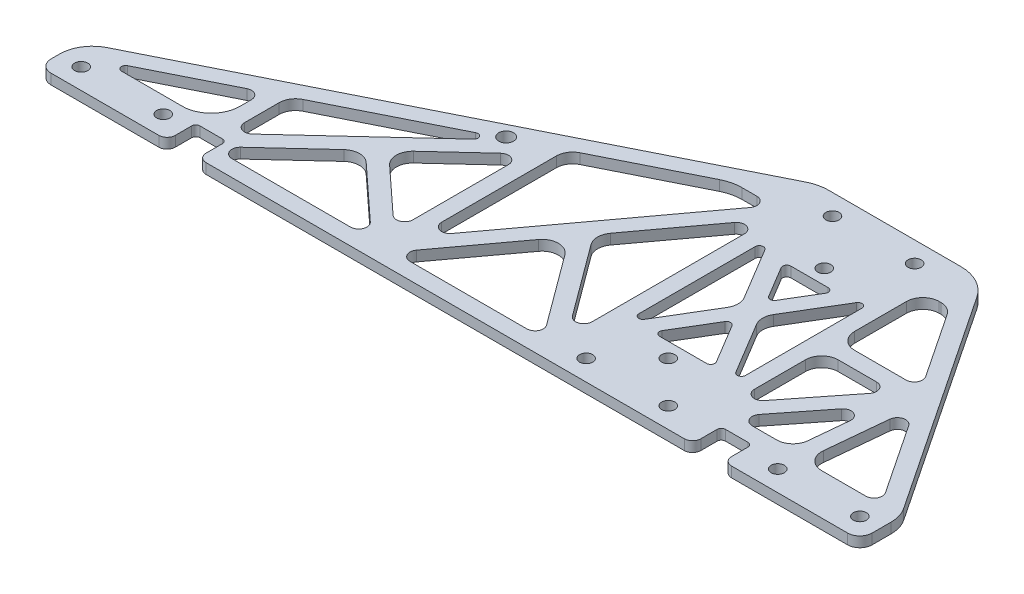
SolidWorks part; units mm, degrees
ref_plane "Front Plane" through (0, 0, 0) normal (0, 0, 1) x (1, 0, 0)
ref_plane "Top Plane" through (0, 0, 0) normal (0, 1, 0) x (1, 0, 0)
ref_plane "Right Plane" through (0, 0, 0) normal (1, 0, 0) x (0, 0, -1)
sketch "Sketch1" plane through (0, 0, 0) normal (0, 1, 0) x (1, 0, 0)
  line L0 (0, 0) -> (254, 0)
  line L2 (203.2, 88.9) -> (152.4, 88.9)
  line L4 (0, 0) -> (0, 12.7)
  line L5 (0, 12.7) -> (152.4, 88.9)
  line L6 (203.2, 88.9) -> (254, 12.7)
  line L7 (254, 12.7) -> (254, 0)
  line L8 (0, 6.35) -> (44.45, 6.35) construction
  line L9 (254, 6.35) -> (222.25, 6.35) construction
  line L10 (139.7, 82.55) -> (207.4333, 82.55) construction
  line L11 (44.45, 0) -> (44.45, 34.925) construction
  line L12 (156.6333, 12.7) -> (154.0933, 7.62)
  line L13 (224.7006, 47.4909) -> (221.314, 12.7) construction
  line L20 (127, 76.2) -> (211.6667, 76.2)
  line L21 (154.0933, 76.2) -> (101.6, 5.08) construction
  line L22 (154.0933, 12.7) -> (154.0933, 7.62)
  line L23 (247.8946, 12.7) -> (194.7333, 12.7)
  line L24 (224.7006, 47.4909) -> (197.2733, 12.7) construction
  line L28 (224.7006, 47.4909) -> (194.7333, 47.4909) construction
  line L31 (5.08, 9.5604) -> (153.5992, 83.82)
  line L32 (200.4813, 83.82) -> (153.5992, 83.82)
  line L33 (200.4813, 83.82) -> (248.92, 11.1619)
  line L34 (248.92, 11.1619) -> (248.92, 5.08)
  line L35 (5.08, 5.08) -> (248.92, 5.08)
  line L36 (5.08, 5.08) -> (5.08, 9.5604)
  line L37 (101.6, 5.08) -> (101.6, 57.8204) construction
  line L39 (127.8467, 40.64) -> (154.0933, 5.08) construction
  line L40 (101.6, 57.8204) -> (44.45, 5.08) construction
  line L41 (73.025, 31.4502) -> (101.6, 5.08) construction
  line L42 (154.0933, 7.62) -> (154.0933, 5.08)
  line L83 (152.8233, 5.08) -> (150.2833, 0)
  line L84 (125.803, 39.1316) -> (152.0497, 3.5716)
  line L107 (152.0497, 77.7084) -> (99.5564, 6.5884)
  line L108 (156.6333, 76.2) -> (194.7333, 12.7) construction
  line L113 (194.7333, 76.2) -> (156.6333, 12.7) construction
  line L117 (104.14, 5.08) -> (104.14, 63.6207)
  line L118 (156.6333, 12.7) -> (194.7333, 12.7)
  line L119 (194.7333, 12.7) -> (201.0833, 0)
  line L120 (154.0933, 6.35) -> (197.9083, 6.35) construction
  line L126 (192.5553, 77.5068) -> (154.4553, 14.0068)
  line L127 (154.4553, 74.8932) -> (192.5553, 11.3932)
  line L128 (156.6333, 12.7) -> (156.6333, 76.2) construction
  line L129 (194.7333, 12.7) -> (194.7333, 76.2) construction
  line L130 (197.2733, 12.7) -> (197.2733, 76.2)
  line L131 (159.1733, 12.7) -> (159.1733, 76.2)
  line L132 (192.1933, 12.7) -> (192.1933, 76.2)
  line L133 (154.0933, 12.7) -> (154.0933, 76.2)
  line L147 (196.9114, 74.8932) -> (158.8114, 11.3932)
  line L148 (158.8114, 77.5068) -> (196.9114, 14.0068)
  line L154 (104.14, 63.6207) -> (42.7274, 6.9466)
  line L155 (71.3024, 29.5836) -> (99.8774, 3.2134)
  line L156 (224.7006, 50.0309) -> (194.7333, 50.0309)
  line L157 (222.7059, 49.0635) -> (195.2786, 14.2725)
  line L158 (197.2733, 12.7) -> (197.2733, 7.62)
  line L159 (222.1726, 47.737) -> (218.7859, 12.9461)
  line L160 (129.8903, 42.1484) -> (156.137, 6.5884)
  line L163 (156.137, 74.6916) -> (103.6436, 3.5716)
  line L164 (99.06, 5.08) -> (99.06, 52.0201)
  line L165 (99.06, 52.0201) -> (46.1726, 3.2134)
  line L166 (175.6833, 19.05) -> (162.9833, 6.35) construction
  line L167 (175.6833, 19.05) -> (188.3833, 6.35) construction
  line L168 (162.9833, 82.55) -> (175.6833, 67.31) construction
  line L169 (175.6833, 67.31) -> (188.3833, 82.55) construction
  line L170 (161.6625, 21.082) -> (189.7041, 21.082) construction
  line L171 (161.6625, 23.622) -> (189.7041, 23.622)
  line L172 (163.1865, 65.278) -> (188.1801, 65.278) construction
  line L173 (163.1865, 62.738) -> (188.1801, 62.738)
  line L174 (74.7476, 33.3168) -> (103.3226, 6.9466)
  line L175 (224.7006, 44.9509) -> (194.7333, 44.9509)
  line L176 (226.6953, 45.9184) -> (199.268, 11.1275)
  line L177 (227.2287, 47.2449) -> (223.842, 12.4539)
  line L178 (8.8192, 11.43) -> (44.45, 11.43)
  line L179 (46.99, 0) -> (46.99, 34.925)
  line L180 (41.91, 0) -> (41.91, 34.925)
  line L181 (198.2745, 13.97) -> (221.4376, 13.97)
  circle A0 centre (6.7733, 6.35) radius 2.032
  circle A1 centre (32.1733, 6.35) radius 2.032
  circle A2 centre (222.25, 6.35) radius 2.032
  circle A3 centre (247.65, 6.35) radius 2.032
  circle A4 centre (162.9833, 82.55) radius 2.032
  circle A5 centre (188.3833, 82.55) radius 2.032
  circle A28 centre (162.9833, 6.35) radius 2.032
  circle A29 centre (188.3833, 6.35) radius 2.032
  arc A32 (197.2733, 12.7) -> (192.1933, 12.7) centre (194.7333, 12.7) cw
  arc A33 (197.2733, 76.2) -> (192.1933, 76.2) centre (194.7333, 76.2) ccw
  arc A34 (159.1733, 12.7) -> (154.0933, 12.7) centre (156.6333, 12.7) cw
  arc A35 (159.1733, 76.2) -> (154.0933, 76.2) centre (156.6333, 76.2) ccw
  arc A45 (192.5553, 77.5068) -> (196.9114, 74.8932) centre (194.7333, 76.2) cw
  arc A46 (154.4553, 14.0068) -> (158.8114, 11.3932) centre (156.6333, 12.7) ccw
  arc A47 (154.4553, 74.8932) -> (158.8114, 77.5068) centre (156.6333, 76.2) cw
  arc A48 (192.5553, 11.3932) -> (196.9114, 14.0068) centre (194.7333, 12.7) ccw
  circle A59 centre (175.6833, 19.05) radius 2.032
  circle A60 centre (175.6833, 67.31) radius 2.032
  arc A61 (125.803, 39.1316) -> (129.8903, 42.1484) centre (127.8467, 40.64) cw
  arc A62 (152.0497, 3.5716) -> (156.137, 6.5884) centre (154.0933, 5.08) ccw
  arc A63 (152.0497, 77.7084) -> (156.137, 74.6916) centre (154.0933, 76.2) cw
  arc A64 (99.5564, 6.5884) -> (103.6436, 3.5716) centre (101.6, 5.08) ccw
  arc A65 (104.14, 5.08) -> (99.06, 5.08) centre (101.6, 5.08) cw
  arc A66 (42.7274, 6.9466) -> (46.1726, 3.2134) centre (44.45, 5.08) ccw
  arc A67 (71.3024, 29.5836) -> (74.7476, 33.3168) centre (73.025, 31.4502) cw
  arc A68 (99.8774, 3.2134) -> (103.3226, 6.9466) centre (101.6, 5.08) ccw
  arc A69 (224.7006, 50.0309) -> (224.7006, 44.9509) centre (224.7006, 47.4909) cw
  arc A70 (194.7333, 50.0309) -> (194.7333, 44.9509) centre (194.7333, 47.4909) ccw
  arc A71 (222.7059, 49.0635) -> (226.6953, 45.9184) centre (224.7006, 47.4909) cw
  arc A72 (195.2786, 14.2725) -> (199.268, 11.1275) centre (197.2733, 12.7) ccw
  arc A73 (222.1726, 47.737) -> (227.2287, 47.2449) centre (224.7006, 47.4909) cw
  arc A74 (218.7859, 12.9461) -> (223.842, 12.4539) centre (221.314, 12.7) ccw
  arc A75 (46.99, 0) -> (41.91, 0) centre (44.45, 0) cw
  arc A76 (46.99, 34.925) -> (41.91, 34.925) centre (44.45, 34.925) ccw
  dimension "D7" = 4.064
  dimension "D8" = 25.4
  dimension "D9" = 130.81
  dimension "D10" = 25.4
  dimension "D11" = 6.35
  dimension "D13" = 19.05
  dimension "D1" = 254
  dimension "D2" = 50.8
  dimension "D3" = 88.9
  dimension "D4" = 152.4
  dimension "D5" = 12.7
  dimension "D6" = 6.35
  dimension "D12" = 25.4
  dimension "D14" = 44.45
  dimension "D15" = 12.7
  dimension "D16" = 57.15
  dimension "D18" = 12.7
  dimension "D19" = 2.54
  dimension "D20" = 50.8
  dimension "D21" = 25.4
  dimension "D22" = 2.54
  dimension "D23" = 6.35
  dimension "D24" = 2.54
  dimension "D29" = 6.35
  dimension "D30" = 38.1
  dimension "D31" = 25.4
  dimension "D32" = 6.35
  dimension "D33" = 2.54
  dimension "D36" = 12.7
  dimension "D38" = 15.24
  dimension "D39" = 2.54
  dimension "D40" = 2.54
  dimension "D27" = 1.27
  dimension "D17" = 5.08
  dimension "D25" = 2.54
  dimension "D26" = 2.54
  dimension "D37" = 2.54
extrude "Boss-Extrude1" add sketch "Sketch1" along normal blind 3.175 contours L0 L7 L6 L2 L5 L4 | A0 | A1 | A5 | A4 | A2 | A3
extrude "Cut-Extrude2" cut sketch "Sketch1<3>" along normal through all contours L154 L31 L11 | L155 L165 L35 | L165 L174 L164 | L117 L107 L20 L31 | L84 L163 L35 | L133 L163 L160 L22 | L157 L175 L130 | L156 L33 L20 L130 | L147 L148 L132 | L131 L126 L127 | L173 L148 L126 | L147 L171 L127 | L33 L177 L23 | L178 L180 L31 | L176 L181 L159 | A28 | A59 | A29 | A60 region at (30.8797, 0, -16.9451) region at (73.025, 0, -12.718) region at (62.4687, 0, -31.7097) region at (120.7695, 0, -51.2726) region at (127.8467, 0, -15.5076) region at (91.6301, 0, -31.4502) region at (206.5243, 0, -60.8789) region at (146.3968, 0, -40.64) region at (204.6702, 0, -35.5682) region at (175.6833, 0, -28.919) region at (187.6774, 0, -44.45) region at (213.9093, 0, -22.3524) region at (163.6893, 0, -44.45) region at (232.896, 0, -23.1836) region at (175.6833, 0, -58.2876)
sketch "Sketch1<3>" plane through (0, 0, 0) normal (0, 1, 0) x (1, 0, 0) same geometry as "Sketch1"
fillet "Fillet1" radius 3.81 2 edges at (254, 1.5875, 0) (0, 1.5875, 0)
fillet "Fillet2" radius 10.16 2 edges at (254, 1.5875, -12.7) (0, 1.5875, -12.7)
fillet "Fillet3" radius 12.7 2 edges at (203.2, 1.5875, -88.9) (152.4, 1.5875, -88.9)
fillet "Fillet4" radius 1.27 12 edges at (159.1733, 1.5875, -67.0298) (192.1933, 1.5875, -67.0298) (192.1933, 1.5875, -21.8702) (159.1733, 1.5875, -21.8702) (183.694, 1.5875, -62.738) (167.6727, 1.5875, -62.738) (175.6833, 1.5875, -49.3869) (185.218, 1.5875, -23.622) (166.1487, 1.5875, -23.622) (175.6833, 1.5875, -39.5131) (93.426, 1.5875, -53.7334) (8.8192, 1.5875, -11.43)
fillet "Fillet5" radius 2.54 19 edges at (223.0073, 1.5875, -50.0309) (247.8946, 1.5875, -12.7) (226.9275, 1.5875, -44.1507) (221.3335, 1.5875, -39.1171) (197.2733, 1.5875, -16.8027) (219.4639, 1.5875, -44.9509) (104.14, 1.5875, -12.7984) (99.06, 1.5875, -52.0201) (48.1953, 1.5875, -5.08) (97.8547, 1.5875, -5.08) (99.06, 1.5875, -10.8803) (104.7569, 1.5875, -5.08) (150.9364, 1.5875, -5.08) (154.0933, 1.5875, -9.3572) (154.0933, 1.5875, -71.9228) (150.9364, 1.5875, -76.2) (41.91, 1.5875, -27.9754) (46.99, 1.5875, -10.8803) (201.5089, 1.5875, -13.97)
fillet "Fillet6" radius 5.08 14 edges at (172.7212, 1.5875, -44.45) (178.6455, 1.5875, -44.45) (223.866, 1.5875, -12.7) (197.2733, 1.5875, -50.0309) (197.2733, 1.5875, -44.9509) (197.2733, 1.5875, -76.2) (205.5613, 1.5875, -76.2) (73.025, 1.5875, -27.9939) (76.7703, 1.5875, -31.4502) (104.14, 1.5875, -59.0904) (131.0036, 1.5875, -40.64) (127.8467, 1.5875, -36.3628) (46.99, 1.5875, -30.5154) (218.8856, 1.5875, -13.97)
fillet "Fillet7" radius 12.7 1 edges at (138.3592, 1.5875, -76.2)
fillet "Fillet10" radius 8.89 1 edges at (41.91, 1.5875, -11.43)
sketch "Sketch2" plane through (0, 3.175, 0) normal (0, 1, 0) x (1, 0, 0)
  line L0 (39.6875, 0) -> (39.6875, 8.89)
  line L1 (3.81, 0) -> (250.19, 0) construction
  line L2 (39.6875, 8.89) -> (49.2125, 8.89)
  line L3 (49.2125, 8.89) -> (49.2125, 0)
  line L4 (0, 3.81) -> (0, 6.4208) construction
  line L5 (202.2475, 0) -> (202.2475, 8.89)
  line L6 (202.2475, 8.89) -> (211.7725, 8.89)
  line L7 (211.7725, 8.89) -> (211.7725, 0)
  line L8 (254, 9.6238) -> (254, 3.81) construction
  line L9 (3.81, 0) -> (250.19, 0)
  dimension "D1" = 39.6875
  dimension "D2" = 9.525
  dimension "D3" = 8.89
  dimension "D4" = 42.2275
extrude "Cut-Extrude3" cut sketch "Sketch2" against normal through all contours L0 L9 L3 L2 | L5 L9 L7 L6 region at (207.01, 3.175, -4.445) region at (44.45, 3.175, -4.445)
fillet "Fillet8" radius 1.27 4 edges at (211.7725, 1.5875, -8.89) (202.2475, 1.5875, -8.89) (49.2125, 1.5875, -8.89) (39.6875, 1.5875, -8.89)
fillet "Fillet9" radius 2.54 4 edges at (49.2125, 1.5875, 0) (39.6875, 1.5875, 0) (211.7725, 1.5875, 0) (202.2475, 1.5875, 0)
sketch "Sketch3" plane through (0, 3.175, 0) normal (0, 1, 0) x (1, 0, 0)
  line L0 (322.9659, 17.0563) -> (94.1827, 68.4886) construction
  circle A0 centre (322.9659, 17.0563) radius 2.286 construction
  circle A1 centre (322.9659, 17.0563) radius 2.286
  circle A2 centre (91.2882, 53.2846) radius 2.286
  arc A4 (94.1827, 68.4886) -> (88.6111, 9.0045) centre (322.9659, 17.0563) ccw construction
  point P5 (91.2665, 53.145)
  point P6 (91.2882, 53.2846)
  dimension "D1" = 234.4931
  dimension "D2" = 4.572
extrude "Cut-Extrude4" cut sketch "Sketch3" against normal up to surface (3.175 mm away) contours A2 region at (91.2882, 3.175, -53.2846) up to face at (233.1564, 0, -22.5815)
